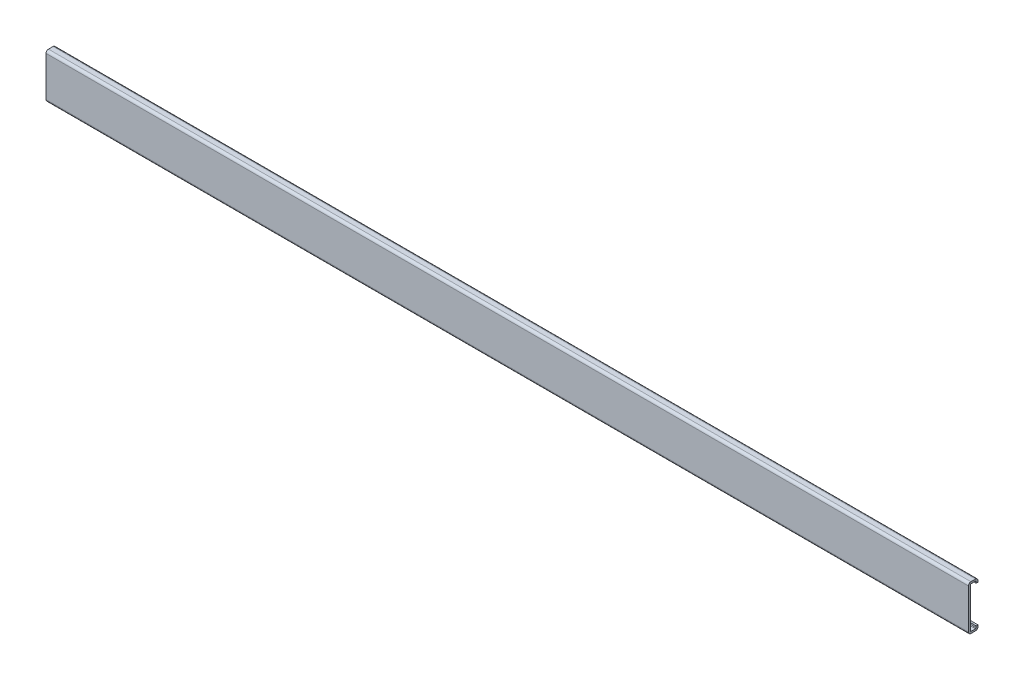
SolidWorks part; units mm, degrees
ref_plane "Спереди" through (0, 0, 0) normal (0, 0, 1) x (1, 0, 0)
ref_plane "Сверху" through (0, 0, 0) normal (0, 1, 0) x (1, 0, 0)
ref_plane "Справа" through (0, 0, 0) normal (1, 0, 0) x (0, 0, -1)
sketch "Эскиз1" plane through (0, 0, 0) normal (1, 0, 0) x (0, 0, -1)
  line L0 (0, -13) -> (0, 13)
  line L1 (-12.4481, 0) -> (26.4522, 0) construction
  line L2 (1, 14) -> (4, 14)
  line L3 (5, 13) -> (5, 12)
  line L4 (5, -13) -> (5, -12)
  line L5 (1, -14) -> (4, -14)
  arc A0 (4, 14) -> (5, 13) centre (4, 13) cw
  arc A1 (0, 13) -> (1, 14) centre (1, 13) cw
  arc A2 (0, -13) -> (1, -14) centre (1, -13) ccw
  arc A3 (4, -14) -> (5, -13) centre (4, -13) ccw
  point P19 (0, 0)
  dimension "D1" = 1
extrude "Вытянуть-Тонкостенный1" add sketch "Эскиз1" along normal blind 600 thin thin type mid plane wall 1.2
